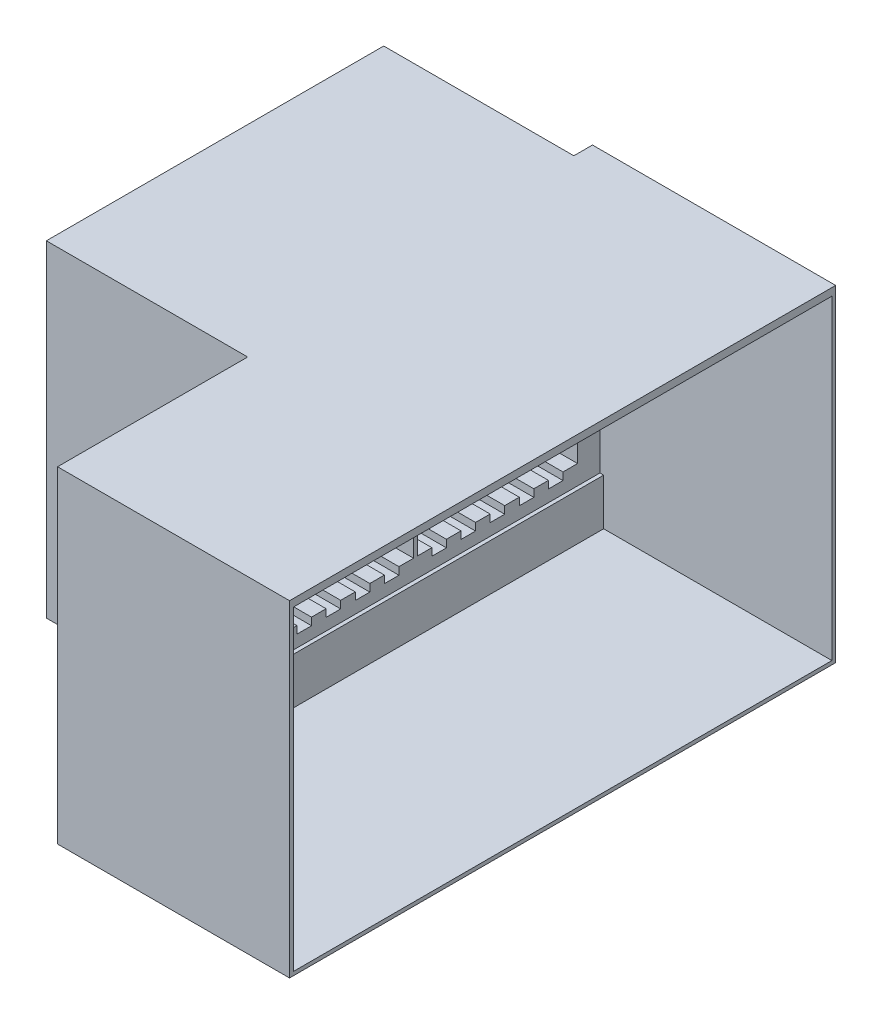
SolidWorks part; units mm, degrees
other "Исправление1"
sketch "Эскиз13" plane through (1050, -360, 1224.5) normal (0.916, -0.3443, 0.206) x (0.3981, 0.8438, -0.36)
ref_plane "Спереди" through (0, 0, 0) normal (0, 0, 1) x (1, 0, 0)
ref_plane "Сверху" through (0, 0, 0) normal (0, 1, 0) x (1, 0, 0)
ref_plane "Справа" through (0, 0, 0) normal (1, 0, 0) x (0, 0, -1)
other "Configuration Table"
sketch "Основа эскиз" plane through (0, 0, 0) normal (1, 0, 0) x (0, 0, -1)
  line L1 (-477.5, 438.28) -> (477.5, 438.28)
  line L2 (-477.5, 438.28) -> (-477.5, -438.28)
  line L3 (-477.5, -438.28) -> (477.5, -438.28)
  line L4 (477.5, 438.28) -> (477.5, -438.28)
  point P4 (0, 438.28)
  point P8 (-477.5, 0)
  dimension "D2" = 955
  dimension "D1" = 876.56
extrude "Основа" add sketch "Основа эскиз" along normal blind 1162.3
sketch "Вырез коретки эскиз" plane through (1162.3, 0, 0) normal (1, 0, 0) x (0, 0, -1)
  line L5 (477.5, 438.28) -> (-477.5, 438.28) construction
  line L6 (-477.5, 418.28) -> (467.5, 418.28)
  line L7 (-477.5, -438.28) -> (477.5, -438.28) construction
  line L8 (-477.5, 418.28) -> (-477.5, -303.68)
  line L9 (-477.5, -303.68) -> (467.5, -303.68)
  line L10 (467.5, 418.28) -> (467.5, -303.68)
  line L11 (-477.5, 438.28) -> (-477.5, -438.28) construction
  line L12 (477.5, -438.28) -> (477.5, 438.28) construction
  point P0 (0, 0)
  dimension "D3" = 10
  dimension "D4" = 134.6
extrude "Вырез коретки" cut sketch "Вырез коретки эскиз" against normal blind 622.3
sketch "вырез ячейки эскиз" plane through (540, 0, 0) normal (1, 0, 0) x (0, 0, -1)
  line L0 (467.5, 418.28) -> (-477.5, 418.28) construction
  line L1 (-462.5, 418.28) -> (-32.5, 418.28)
  line L2 (-462.5, 418.28) -> (-462.5, 98.28)
  line L3 (-462.5, 98.28) -> (-32.5, 98.28)
  line L4 (-32.5, 418.28) -> (-32.5, 98.28)
  line L17 (-477.5, 418.28) -> (-477.5, -303.68) construction
  dimension "D7" = 430
  dimension "D8" = 320
  dimension "D1" = 15
extrude "вырез ячейки" cut sketch "вырез ячейки эскиз" against normal blind 510
sketch "вырез двери эскиз" plane through (0, 0, 0) normal (-1, 0, 0) x (0, 0, 1)
  line L1 (32.5, 418.28) -> (467.5, 418.28)
  line L2 (32.5, 418.28) -> (32.5, 98.28)
  line L3 (32.5, 98.28) -> (467.5, 98.28)
  line L4 (467.5, 418.28) -> (467.5, 98.28)
  line L6 (462.5, 98.28) -> (32.5, 98.28) construction
  line L7 (32.5, 98.28) -> (32.5, 418.28) construction
  line L8 (462.5, 418.28) -> (462.5, 98.28) construction
  line L9 (462.5, 418.28) -> (462.5, 98.28) construction
  line L10 (32.5, 418.28) -> (462.5, 418.28) construction
  dimension "D2" = 5
extrude "вырез двери" cut sketch "вырез двери эскиз" against normal blind 10
sketch "Вырез основание низ эскиз" plane through (0, -303.68, 0) normal (0, 1, 0) x (1, 0, 0)
  line L0 (1162.3, -477.5) -> (1162.3, 467.5) construction
  line L1 (550, 467.5) -> (1152.3, 467.5)
  line L2 (550, 467.5) -> (550, -477.5)
  line L3 (550, -477.5) -> (1152.3, -477.5)
  line L4 (1152.3, 467.5) -> (1152.3, -477.5)
  line L5 (540, 467.5) -> (1162.3, 467.5) construction
  line L6 (540, -477.5) -> (1162.3, -477.5) construction
  dimension "D1" = 10
  dimension "D2" = 602.3
extrude "Вырез основание низ" cut sketch "Вырез основание низ эскиз" against normal blind 124.6
sketch "Вырез основания верх эскиз" plane through (0, 418.28, 0) normal (0, -1, 0) x (1, 0, 0)
  line L0 (540, 477.5) -> (1162.3, 477.5) construction
  line L1 (550, -467.5) -> (1152.3, -467.5)
  line L2 (550, -467.5) -> (550, 477.5)
  line L3 (550, 477.5) -> (1152.3, 477.5)
  line L4 (1152.3, -467.5) -> (1152.3, 477.5)
  line L5 (540, -467.5) -> (1162.3, -467.5) construction
  line L6 (1162.3, -467.5) -> (1162.3, 477.5) construction
  dimension "D1" = 10
  dimension "D2" = 602.3
extrude "Вырез основание верх" cut sketch "Вырез основания верх эскиз" against normal blind 10
sketch "вырез полозья эскиз" plane through (540, 0, 0) normal (1, 0, 0) x (0, 0, -1)
  line L0 (-462.5, 98.28) -> (-32.5, 98.28) construction
  line L1 (-423.4091, 98.28) -> (-384.3182, 98.28)
  line L2 (-423.4091, 98.28) -> (-423.4091, 78.28)
  line L3 (-423.4091, 78.28) -> (-384.3182, 78.28)
  line L4 (-384.3182, 98.28) -> (-384.3182, 78.28)
  dimension "D2" = 39.0909
  dimension "D3" = 39.0909
extrude "Вырез полозья" cut sketch "вырез полозья эскиз" against normal blind 510
pattern_linear "Линейный массив полозьев" count 5 spacing 78.1818 along (0, 0, -1) of "Вырез полозья"
pattern_linear "Линейный массив ячеек" count 2 spacing 440 along (0, 0, -1) count 2 spacing 350 along (0, -1, 0) of "Линейный массив полозьев", "вырез двери", "вырез ячейки"
sketch "Основание эскиз" plane through (0, 0, 477.5) normal (0, 0, 1) x (1, 0, 0)
  line L0 (1162.3, -438.28) -> (1162.3, -303.68)
  line L1 (1162.3, -303.68) -> (1152.3, -303.68)
  line L2 (1152.3, -303.68) -> (1152.3, -428.28)
  line L3 (1152.3, -428.28) -> (550, -428.28)
  line L4 (550, -428.28) -> (550, -303.68)
  line L5 (550, -303.68) -> (540, -303.68)
  line L6 (540, -303.68) -> (540, -438.28)
  line L7 (1162.3, -438.28) -> (0, -438.28) construction
  line L8 (540, -438.28) -> (1162.3, -438.28)
  line L9 (1152.3, 418.28) -> (1162.3, 418.28)
  line L10 (1162.3, 418.28) -> (1162.3, 438.28)
  line L11 (1162.3, 438.28) -> (540, 438.28)
  line L12 (1162.3, 438.28) -> (0, 438.28) construction
  line L13 (540, 438.28) -> (540, 418.28)
  line L14 (540, 418.28) -> (550, 418.28)
  line L15 (550, 418.28) -> (550, 428.28)
  line L16 (550, 428.28) -> (1152.3, 428.28)
  line L17 (1152.3, 428.28) -> (1152.3, 418.28)
extrude "Основание" add sketch "Основание эскиз" along normal blind 500
sketch "Стенка боквая эскиз" plane through (0, 0, 977.5) normal (0, 0, 1) x (1, 0, 0)
  line L1 (1162.3, 438.28) -> (540, 438.28)
  line L2 (1162.3, 438.28) -> (1162.3, -438.28)
  line L3 (1162.3, -438.28) -> (540, -438.28)
  line L4 (540, 438.28) -> (540, -438.28)
extrude "Стенка боковая" add sketch "Стенка боквая эскиз" along normal blind 10
sketch "Эскиз14" plane through (0, 0, -477.5) normal (0, 0, -1) x (-1, 0, 0)
  line L0 (-1162.3, 438.28) -> (0, 438.28) construction
  line L1 (0, -438.28) -> (-510, -438.28)
  line L2 (0, -438.28) -> (0, 438.28)
  line L3 (0, 438.28) -> (-510, 438.28)
  line L4 (-510, -438.28) -> (-510, 438.28)
  dimension "D1" = 510
extrude "Вырез-Вытянуть1" cut sketch "Эскиз14" against normal blind 50
sketch "Эскиз15" plane through (1162.3, 0, 0) normal (1, 0, 0) x (0, 0, -1)
  line L1 (-977.5, -303.68) -> (467.5, -303.68)
  line L2 (-977.5, -303.68) -> (-977.5, -428.28)
  line L3 (-977.5, -428.28) -> (467.5, -428.28)
  line L4 (467.5, -303.68) -> (467.5, -428.28)
extrude "Вырез-Вытянуть2" cut sketch "Эскиз15" against normal up to next
equation "\"Ширина груза\"= 420"
equation "\"Глубина груза\"= 490"
equation "\"Высота груза\"= 297"
equation "\"Ширина ячейки\"= \"Ширина груза\" + 10"
equation "\"Глубина ячейки\"= \"Глубина груза\" + 10"
equation "\"Высота ячейки\"= \"Высота груза\" + 10 + 13"
equation "\"Колво ячеек ширина\"= 2"
equation "\"Колво ячеек высота\"= 2"
equation "\"Толщина стенки\"= 10"
equation "\"D2@Основа эскиз\"=( \"Ширина ячейки\" + \"Толщина стенки\" + \"Крепление дверцы\" ) * \"Колво ячеек ширина\" + \"Ширина пластины\"+\"Толщина стенки\"*1.5"
equation "\"D1@Основа эскиз\"=( \"Высота ячейки\" + \"Толщина стенки\" + \"Высота пола\" ) * \"Колво ячеек высота\" + \"Отступ рейки\" * 2 + \"Высота рейки\" * 2 + \"Толщина стенки\" * 2 + \"Мотор X ширина корпуса\" + \"Мотор Y ширина корпуса\"- 8.04"
equation "\"Крепление дверцы\"= 5"
equation "\"D7@вырез ячейки эскиз\"= \"Ширина ячейки\""
equation "\"D1@вырез ячейки эскиз\" = \"Толщина стенки\" + \"Крепление дверцы\""
equation "\"D8@вырез ячейки эскиз\"= \"Высота ячейки\""
equation "\"D2@вырез двери эскиз\"= \"Крепление дверцы\""
equation "\"D1@Основа\"=\"Глубина ячейки\" + \"Глубина каретки\" + \"Толщина стенки\" * 6 + \"Ширина рейки\""
equation "\"D1@Вырез коретки\"=\"Глубина каретки\" + \"Толщина стенки\" * 2 + \"Ширина рейки\""
equation "\"D1@Вырез основание низ эскиз\"=\"Толщина стенки\" "
equation "\"Ширина рейки\"= \"Толщина шестерни\""
equation "\"D1@вырез ячейки\"= \"Глубина ячейки\" + \"Толщина стенки\""
equation "\"D1@вырез двери\"= \"Толщина стенки\""
equation "\"D2@Вырез основание низ эскиз\"=\"Глубина каретки\" + \"Ширина рейки\""
equation "\"Высота рейки\"= 20"
equation "\"D1@Вырез основания верх эскиз\"=\"Толщина стенки\""
equation "\"D2@Вырез основания верх эскиз\"=\"Глубина каретки\" + \"Ширина рейки\" "
equation "\"D1@Вырез основание верх\"=\"Толщина стенки\""
equation "\"D4@Вырез коретки эскиз\"=\"Толщина стенки\"  + \"Высота рейки\" + \"Отступ рейки\" + \"Мотор X ширина корпуса\" + \"Мотор Y ширина корпуса\""
equation "\"D1@Вырез коретки эскиз\"=\"Толщина стенки\"*2"
equation "\"D3@Вырез коретки эскиз\" = \"Толщина стенки\""
equation "\"D1@Вырез основание низ\"=\"Мотор X ширина корпуса\" + \"Мотор Y ширина корпуса\"+\"Высота рейки\" + \"Отступ рейки\""
equation "\"Высота пола\"= 20"
equation "\"Колво полозьев\"= 5"
equation "\"D1@вырез полозья эскиз\" = \"Высота пола\""
equation "\"D2@вырез полозья эскиз\" = \"Ширина ячейки\" /  ( \"Колво полозьев\" * 2 + 1 ) "
equation "\"D3@вырез полозья эскиз\"= \"Ширина ячейки\" / ( \"Колво полозьев\" * 2 + 1 )"
equation "\"D1@Вырез полозья\" = \"Глубина ячейки\" + \"Толщина стенки\""
equation "\"D1@Линейный массив полозьев\" = \"Колво полозьев\""
equation "\"D3@Линейный массив полозьев\" = \"Ширина ячейки\" /  ( \"Колво полозьев\" * 2 + 1 )  * 2"
equation "\"D1@Линейный массив ячеек\" = \"Колво ячеек ширина\""
equation "\"D2@Линейный массив ячеек\" = \"Колво ячеек высота\""
equation "\"D3@Линейный массив ячеек\" = \"Ширина ячейки\" + \"Толщина стенки\""
equation "\"D4@Линейный массив ячеек\" = \"Высота ячейки\" + \"Высота пола\" + \"Толщина стенки\""
equation "\"Отступ рейки\"= 20"
equation "\"Глубина каретки\"= \"Глубина ячейки\" + 30 + \"Мотор Y высота корпуса\" + 20"
equation "\"D1@Стенка боковая\" = \"Толщина стенки\""
equation "\"Длинна рейки\"= ( \"Ширина ячейки\" + \"Толщина стенки\" + \"Крепление дверцы\" ) * \"Колво ячеек ширина\" + \"Ширина ячейки выгрузки\" * \"Колво выгрузки\" + \"Толщина стенки\""
equation "\"D1@Основание\" = \"Длинна рейки\" -  ( \"Ширина ячейки\" + \"Толщина стенки\" + \"Крепление дверцы\" )  * \"Колво ячеек ширина\" - \"Толщина стенки\""
equation "\"Отступ шпильки\"= 20"
equation "\"Диаметр шпильки\"= 5"
equation "\"Длинна шпильки\"= ( \"Высота ячейки\" + \"Толщина стенки\" + \"Высота пола\" ) * \"Колво ячеек высота\" + ( \"Толщина стенки\" + \"Отступ рейки\" ) * 2 "
equation "\"Ширина пластины\"= 50  "
equation "\"Высота зона выгрузки\"= \"Высота ячейки\" * 2 + \"Толщина стенки\" * 2"
equation "\"Колво выгрузки\"= 1"
equation "\"D1@Эскиз14\"= \"Толщина стенки\" + \"Глубина ячейки\""
equation "\"D1@Вырез-Вытянуть1\"= \"Ширина пластины\""
equation "\"Ширина ячейки выгрузки\"= \"Ширина ячейки\" + \"Толщина стенки\" + \"Отступ крепления мотора фиксации\"*2"
equation "\"Отступ крепления мотора фиксации\" = 30"
equation "\"Мотор X ширина корпуса\"= 42.3"
equation "\"Мотор X высота корпуса\"= 42.3"
equation "\"Мотор X длина корпуса\"= 40"
equation "\"Мотор X вылет вала\"= 19.8"
equation "\"Мотор Y ширина корпуса\"= 42.3"
equation "\"Мотор Y высота корпуса\"= 42.3"
equation "\"Мотор Y длина корпуса\"= 48"
equation "\"Мотор Y вылет вала\"= 30"
equation "\"Мотор Z ширина корпуса\"= 42"
equation "\"Мотор Z высота корпуса\"= 42"
equation "\"Мотор Z длина корпуса\"= 40"
equation "\"Мотор Z вылет вала\"= 23"
equation "\"Мотор диаметр вала ПРЕДВ\"= 5"
equation "\"Мотор шаг крепления ПРЕДВ\"= 31"
equation "\"Мотор диаметр отверстий ПРЕДВ\"= 3"
equation "\"Мотор глубина отверстий ПРЕДВ\"= 4.5"
equation "\"Мотор диаметр буртика ПРЕДВ\"= 22"
equation "\"Мотор высота буртика ПРЕДВ\"= 2"
equation "\"Мотор диаметр шкива ПРЕДВ\"= 16"
equation "\"Мотор длина шкива ПРЕДВ\"= 12"
equation "\"Мотор отступ шкива ПРЕДВ\"= 5"
equation "\"Мотор X шаг градусов\"= 1.8"
equation "\"Мотор Y шаг градусов\"= 1.8"
equation "\"Мотор Z шаг градусов\"= 1.8"
equation "\"Мотор Y диаметр ротора\"= 25.78"
equation "\"Толщина шестерни\"= 10"
